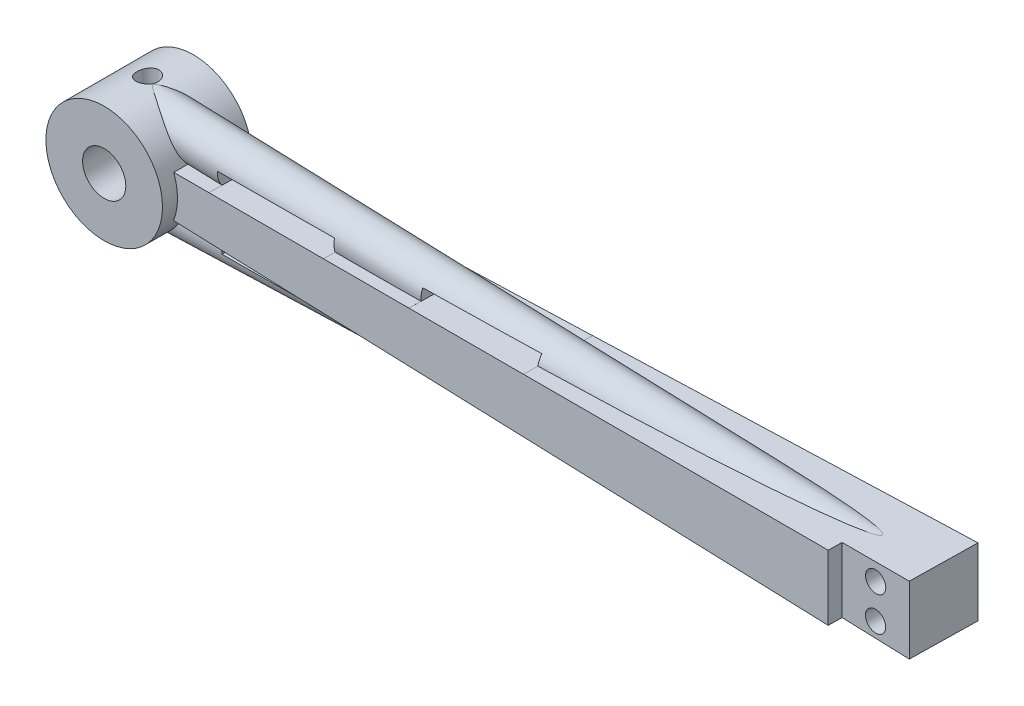
SolidWorks part; units mm, degrees
ref_plane "Front Plane" through (0, 0, 0) normal (0, 0, 1) x (1, 0, 0)
ref_plane "Top Plane" through (0, 0, 0) normal (0, 1, 0) x (1, 0, 0)
ref_plane "Right Plane" through (0, 0, 0) normal (1, 0, 0) x (0, 0, -1)
sketch "Sketch2" plane through (0, 0, 0) normal (0, 0, 1) x (1, 0, 0)
  circle A0 centre (0, 0) radius 8.5
  dimension "D1" = 17
extrude "Boss-Extrude1" add sketch "Sketch2" along normal blind 13
ref_plane "Plane1" through (5, 0, 0) normal (1, 0, 0) x (0, 0, -1)
sketch "Sketch4" plane through (5, 0, 0) normal (1, 0, 0) x (0, 0, -1)
  line L1 (-10.7522, 2.9653) -> (-2.7522, 2.9653)
  line L2 (-10.7522, 2.9653) -> (-10.7522, -3.0347)
  line L3 (-10.7522, -3.0347) -> (-2.7522, -3.0347)
  line L4 (-2.7522, 2.9653) -> (-2.7522, -3.0347)
  line L5 (-10.7522, 2.9653) -> (-2.7522, -3.0347) construction
  line L6 (-10.7522, -3.0347) -> (-2.7522, 2.9653) construction
  point P0 (-6.7522, -0.0347)
  dimension "D1" = 6
  dimension "D2" = 8
extrude "Boss-Extrude2" add sketch "Sketch4" along normal blind 150 draft 1 draft outward yes
ref_axis "Axis2" through (0, 0, -0.6511) along (0, 0, 1)
ref_plane "Plane2" through (0, 0, 0) normal (-0.9994, 0.0349, 0) x (0, 0, 1)
ref_plane "Plane3" through (0, 0, 0) normal (0.9994, 0.0349, 0) x (0, 0, 1)
sketch "Sketch6" plane through (0, 0, 0) normal (-0.9994, 0.0349, 0) x (0, 0, 1)
  circle A0 centre (6.6819, 5.4831) radius 3
  dimension "D1" = 6
extrude "Boss-Extrude3" add sketch "Sketch6" against normal blind 120
sketch "Sketch7" plane through (0, 0, 0) normal (0.9994, 0.0349, 0) x (0, 0, 1)
  circle A0 centre (6.3159, 5.4318) radius 3
  dimension "D1" = 6
extrude "Boss-Extrude4" add sketch "Sketch7" along normal blind 120
sketch "Sketch8" plane through (0, 0, 13) normal (0, 0, 1) x (1, 0, 0)
  circle A0 centre (0, 0) radius 3.15
  dimension "D1" = 6.3
extrude "Cut-Extrude2" cut sketch "Sketch8" against normal up to next
sketch "Sketch9" plane through (-0.1861, 0, 10.6617) normal (-0.0175, 0, 0.9998) x (0.9998, 0, 0.0175)
  line L0 (13.3377, 3.1076) -> (30.3377, 3.4043)
  line L1 (155.2097, 5.5836) -> (8.134, 3.0168) construction
  line L2 (30.3377, 3.4043) -> (30.3377, 5.2185)
  line L3 (30.3377, 5.2185) -> (13.3377, 5.2185)
  line L4 (13.3377, 5.2185) -> (13.3377, 3.1076)
  line L5 (43.0187, 3.6256) -> (60.0187, 3.9223)
  line L6 (60.0187, 3.9223) -> (60.0187, 5.2185)
  line L7 (60.0187, 5.2185) -> (43.0187, 5.2185)
  line L8 (43.0187, 5.2185) -> (43.0187, 3.6256)
  line L9 (13.6245, -3.1819) -> (30.6245, -3.4786)
  line L10 (155.2097, -5.6529) -> (8.1075, -3.0856) construction
  line L11 (30.6245, -3.4786) -> (30.6245, -5.3206)
  line L12 (30.6245, -5.3206) -> (13.6245, -5.3206)
  line L13 (13.6245, -5.3206) -> (13.6245, -3.1819)
  line L14 (43.0187, -3.6949) -> (60.0187, -3.9916)
  line L15 (60.0187, -3.9916) -> (60.0187, -5.3206)
  line L16 (60.0187, -5.3206) -> (43.0187, -5.3206)
  line L17 (43.0187, -5.3206) -> (43.0187, -3.6949)
  dimension "D1" = 17
  dimension "D2" = 17
  dimension "D3" = 17
  dimension "D4" = 17
extrude "Cut-Extrude3" cut sketch "Sketch9" against normal up to next
sketch "Sketch12" plane through (-0.0502, 2.8772, 0) normal (-0.0175, 0.9998, 0) x (0.9998, 0.0175, 0)
  line L5 (136.4064, -11.3608) -> (146.4064, -11.3608)
  line L6 (136.4064, -11.3608) -> (136.4064, -9.309)
  line L7 (136.4064, -9.309) -> (146.4064, -9.309)
  line L8 (146.4064, -11.3608) -> (146.4064, -9.309)
  dimension "D3" = 10
extrude "Cut-Extrude6" cut sketch "Sketch12" against normal up to next
sketch "Sketch13" plane through (-0.1861, 0, 10.6617) normal (-0.0175, 0, 0.9998) x (0.9998, 0, 0.0175)
  line L0 (155.2097, 5.5836) -> (155.2097, -5.6529) construction
  line L1 (158.9167, 9.2795) -> (115.2097, 9.2795)
  line L2 (158.9167, 9.2795) -> (158.9167, -18.7488)
  line L3 (158.9167, -18.7488) -> (115.2097, -18.7488)
  line L4 (115.2097, 9.2795) -> (115.2097, -18.7488)
  dimension "D1" = 40
extrude "Cut-Extrude7" cut sketch "Sketch13" against normal up to surface (13.372 mm away) up to face at (45.6954, -0.0358, 2.0418)
sketch "Sketch14" plane through (-0.1861, 0, 10.6617) normal (-0.0175, 0, 0.9998) x (0.9998, 0, 0.0175)
  line L6 (115.2432, -6.1562) -> (105.2432, -6.1562)
  line L7 (115.2432, -6.1562) -> (115.2432, 7.7127)
  line L8 (115.2432, 7.7127) -> (105.2432, 7.7127)
  line L9 (105.2432, -6.1562) -> (105.2432, 7.7127)
  dimension "D1" = 10
extrude "Cut-Extrude8" cut sketch "Sketch14" against normal blind 2
sketch "Sketch15" plane through (-0.1512, 0, 8.662) normal (-0.0175, 0, 0.9998) x (0.9998, 0, 0.0175)
  line L0 (115.2097, 4.8861) -> (105.2432, 4.7122) construction
  line L1 (115.2097, -4.9554) -> (115.2097, 4.8861) construction
  circle A0 centre (110.2202, 2.2977) radius 1.5
  circle A2 centre (110.2097, -2.7023) radius 1.5
  dimension "D1" = 3
  dimension "D2" = 3
  dimension "D3" = 7.5
  dimension "D4" = 5
  dimension "D5" = 5
extrude "Cut-Extrude9" cut sketch "Sketch15" against normal up to next
sketch "Sketch16" plane through (0, 0, 0) normal (0, 1, 0) x (1, 0, 0)
  circle A0 centre (-0.736, -5.9503) radius 1.55
  dimension "D1" = 3.1
extrude "Cut-Extrude10" cut sketch "Sketch16" against normal mid plane 20
